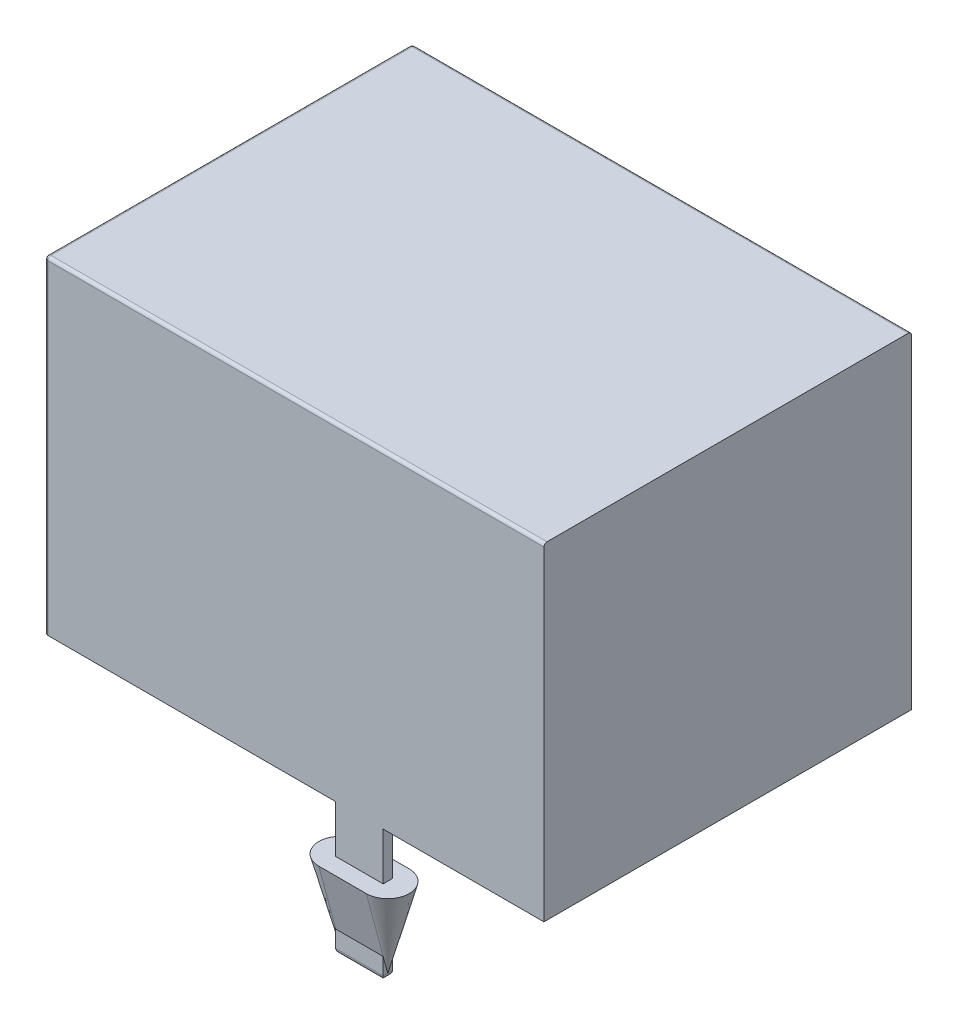
SolidWorks part; units mm, degrees
ref_plane "Plan de face" through (0, 0, 0) normal (0, 0, 1) x (1, 0, 0)
ref_plane "Plan de dessus" through (0, 0, 0) normal (0, 1, 0) x (1, 0, 0)
ref_plane "Plan de droite" through (0, 0, 0) normal (1, 0, 0) x (0, 0, -1)
sketch "Esquisse1" plane through (0, 0, 0) normal (0, 1, 0) x (1, 0, 0)
  line L1 (0, 0) -> (-16.3, 0)
  line L2 (0, 0) -> (0, 12)
  line L3 (0, 12) -> (-16.3, 12)
  line L4 (-16.3, 0) -> (-16.3, 12)
  dimension "D1" = 12
  dimension "D2" = 16.3
extrude "Boss.-Extru.1" add sketch "Esquisse1" along normal blind 10.7
sketch "Esquisse2" plane through (-16.3, 0, 0) normal (-1, 0, 0) x (0, 0, 1)
  line L0 (-8.6, 9.25) -> (-10.2, 7.65)
  line L1 (-10.2, 1.65) -> (-1.8, 1.65)
  line L2 (-10.2, 1.65) -> (-10.2, 7.65)
  line L3 (-8.6, 9.25) -> (-3.4, 9.25)
  line L4 (-1.8, 1.65) -> (-1.8, 7.65)
  line L5 (-3.4, 9.25) -> (-1.8, 7.65)
  line L6 (-6, 9.25) -> (-6, 1.65) construction
  line L7 (-6, 10.7) -> (-6, 0) construction
  line L8 (-12, 10.7) -> (0, 10.7) construction
  line L9 (-12, 0) -> (0, 0) construction
  dimension "D2" = 5.2
  dimension "D3" = 45
  dimension "D4" = 45
  dimension "D5" = 8.4
  dimension "D6" = 7.6
  dimension "D7" = 1.45
extrude "Enlèv. mat.-Extru.1" cut sketch "Esquisse2" against normal blind 9
sketch "Esquisse4" plane through (-7.3, 0, 0) normal (-1, 0, 0) x (0, 0, 1)
  line L0 (-6, 6.95) -> (-6, 3.85) construction
  line L1 (-8.8, 6.95) -> (-3.2, 6.95)
  line L2 (-8.8, 6.95) -> (-8.8, 3.85)
  line L3 (-8.8, 3.85) -> (-3.2, 3.85)
  line L4 (-3.2, 6.95) -> (-3.2, 3.85)
  line L5 (-6, 9.25) -> (-6, 1.65) construction
  line L6 (-3.4, 9.25) -> (-8.6, 9.25) construction
  line L7 (-10.2, 1.65) -> (-1.8, 1.65) construction
  dimension "D1" = 5.6
  dimension "D2" = 3.1
  dimension "D3" = 2.2
extrude "Boss.-Extru.2" add sketch "Esquisse4" along normal blind 8.8
chamfer "Chanfrein1" distance 0.2 angle 45 14 edges at (-11.7, 3.85, -8.8) (-16.1, 3.85, -6) (-11.7, 3.85, -3.2) (-11.7, 6.95, -3.2) (-16.1, 5.4, -3.2) (-16.1, 5.4, -8.8) (-11.7, 6.95, -8.8) (-16.1, 6.95, -6) (-16.3, 1.65, -6) (-16.3, 4.65, -1.8) (-16.3, 8.45, -2.6) (-16.3, 9.25, -6) (-16.3, 8.45, -9.4) (-16.3, 4.65, -10.2)
fillet "Congé1" radius 0.1 6 edges at (-16.3, 0, -6) (-16.3, 5.35, -12) (-8.15, 10.7, -12) (-16.3, 5.35, 0) (-16.3, 10.7, -6) (-8.15, 10.7, 0)
sketch "Esquisse5" plane through (0, 0, 0) normal (0, -1, 0) x (1, 0, 0)
  line L0 (-16.2, 0) -> (0, 0) construction
  line L1 (-6.8, 0) -> (-5.25, 0)
  line L2 (-6.8, 0) -> (-6.8, -0.3)
  line L3 (-6.8, -0.3) -> (-5.25, -0.3)
  line L4 (-5.25, 0) -> (-5.25, -0.3)
  line L5 (0, -6) -> (-16.2, -6) construction
  line L6 (0, 0) -> (0, -12) construction
  line L7 (-16.2, 0) -> (-16.2, -12) construction
  line L8 (-5.25, -12) -> (-5.25, -11.7)
  line L9 (-6.8, -11.7) -> (-5.25, -11.7)
  line L10 (-6.8, -12) -> (-6.8, -11.7)
  line L11 (-6.8, -12) -> (-5.25, -12)
  dimension "D1" = 0.3
  dimension "D2" = 1.55
  dimension "D3" = 9.4
extrude "Boss.-Extru.3" add sketch "Esquisse5" along normal blind 4.3
ref_plane "Plan1" through (0, -1.55, 0) normal (0, 1, 0) x (1, 0, 0)
sketch "Esquisse6" plane through (0, -1.55, 0) normal (0, 1, 0) x (1, 0, 0)
  line L0 (-6.8, 0.15) -> (-5.25, 0.15) construction
  line L1 (-6.8, 0) -> (-6.8, 0.3) construction
  line L2 (-5.25, 0.3) -> (-5.25, 0) construction
  line L3 (-6.8, 0.85) -> (-5.25, 0.85)
  line L4 (-6.8, -0.55) -> (-5.25, -0.55)
  line L5 (-6.8, 11.85) -> (-5.25, 11.85) construction
  line L6 (-6.8, 11.7) -> (-6.8, 12) construction
  line L7 (-5.25, 12) -> (-5.25, 11.7) construction
  line L8 (-6.8, 12.55) -> (-5.25, 12.55)
  line L9 (-6.8, 11.15) -> (-5.25, 11.15)
  arc A0 (-6.8, 0.85) -> (-6.8, -0.55) centre (-6.8, 0.15) ccw
  arc A1 (-5.25, -0.55) -> (-5.25, 0.85) centre (-5.25, 0.15) ccw
  arc A2 (-6.8, 12.55) -> (-6.8, 11.15) centre (-6.8, 11.85) ccw
  arc A3 (-5.25, 11.15) -> (-5.25, 12.55) centre (-5.25, 11.85) ccw
  point P6 (-6.025, 0.15)
  point P17 (-6.025, 11.85)
  dimension "D1" = 0.7
  dimension "D2" = 0.7
extrude "Boss.-Extru.4" add sketch "Esquisse6" against normal blind 2.6 draft 15
fillet "Congé3" radius 0.15 8 edges at (-6.8, -4.3, -11.85) (-6.025, -4.3, -11.7) (-5.25, -4.3, -11.85) (-6.025, -4.3, -12) (-6.025, -4.3, 0) (-5.25, -4.3, -0.15) (-6.025, -4.3, -0.3) (-6.8, -4.3, -0.15)
